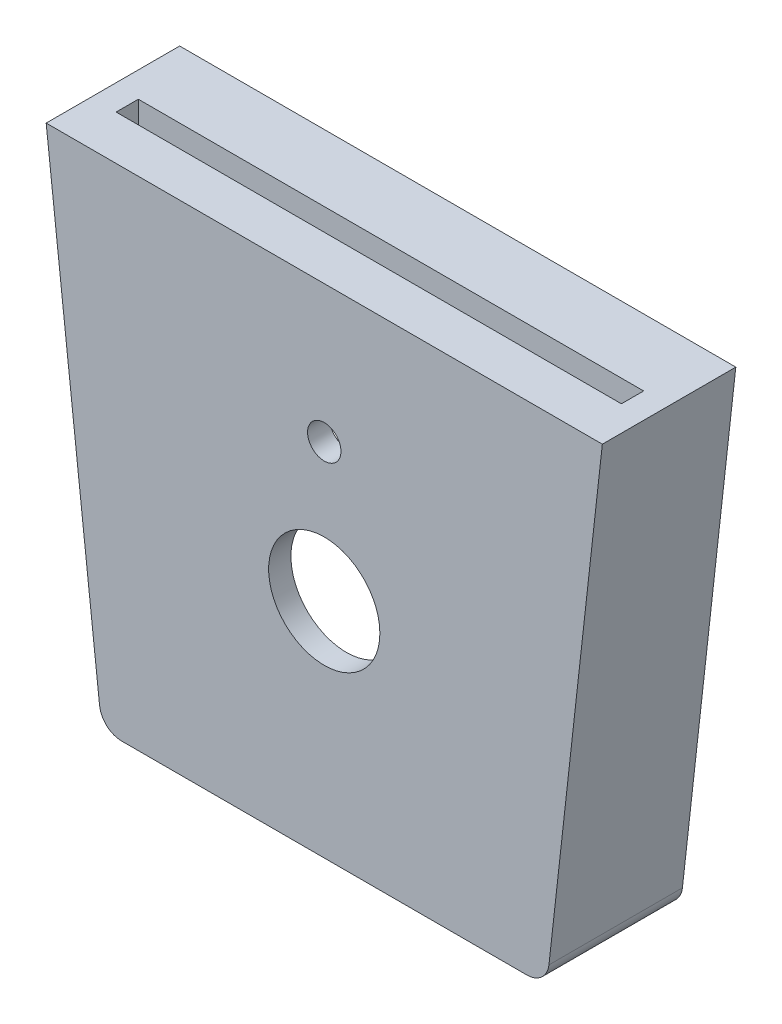
SolidWorks part; units mm, degrees
ref_plane "Front Plane" through (0, 0, 0) normal (0, 0, 1) x (1, 0, 0)
ref_plane "Top Plane" through (0, 0, 0) normal (0, 1, 0) x (1, 0, 0)
ref_plane "Right Plane" through (0, 0, 0) normal (1, 0, 0) x (0, 0, -1)
sketch "Sketch1" plane through (0, 0, 0) normal (0, 0, 1) x (1, 0, 0)
  line L0 (0, 56.7961) -> (0, -56.7961) construction
  line L1 (63.5, 56.7961) -> (-63.5, 56.7961)
  line L2 (-63.5, 56.7961) -> (-51.3049, -52.2806)
  line L3 (-46.2563, -56.7961) -> (46.2563, -56.7961)
  line L4 (63.5, 56.7961) -> (51.3049, -52.2806)
  arc A0 (-51.3049, -52.2806) -> (-46.2563, -56.7961) centre (-46.2563, -51.7161) ccw
  arc A1 (51.3049, -52.2806) -> (46.2563, -56.7961) centre (46.2563, -51.7161) cw
  circle A2 centre (0, 25.5165) radius 3.81
  circle A3 centre (0, -5.9961) radius 12.7
  point P10 (-50.8, -56.7961)
  dimension "D4" = 5.08
  dimension "D6" = 7.62
  dimension "D7" = 25.4
  dimension "D8" = 31.2797
  dimension "D9" = 50.8
  dimension "D1" = 50.8
  dimension "D2" = 63.5
  dimension "D3" = 56.7961
  dimension "D5" = 109.0767
extrude "Boss-Extrude1" add sketch "Sketch1" against normal blind 5.08
sketch "Sketch2" plane through (0, 0, -5.08) normal (0, 0, 1) x (1, 0, 0)
  line L0 (0, 56.7961) -> (0, -56.7961) construction
  line L1 (63.5, 56.7961) -> (-63.5, 56.7961)
  line L2 (-63.5, 56.7961) -> (-51.3049, -52.2806)
  line L3 (-46.2563, -56.7961) -> (46.2563, -56.7961)
  line L4 (63.5, 56.7961) -> (51.3049, -52.2806)
  line L5 (-46.2563, -56.7961) -> (46.2563, -56.7961) construction
  line L6 (-57.8204, 51.7161) -> (57.8204, 51.7161)
  line L7 (57.8204, 51.7161) -> (46.7612, -47.2006)
  line L8 (41.7126, -51.7161) -> (-41.7126, -51.7161)
  line L9 (-57.8204, 51.7161) -> (-46.7612, -47.2006)
  arc A0 (-51.3049, -52.2806) -> (-46.2563, -56.7961) centre (-46.2563, -51.7161) ccw
  arc A1 (51.3049, -52.2806) -> (46.2563, -56.7961) centre (46.2563, -51.7161) cw
  circle A2 centre (0, 26.1693) radius 3.81
  circle A3 centre (0, -32.9791) radius 12.7
  arc A4 (46.7612, -47.2006) -> (41.7126, -51.7161) centre (41.7126, -46.6361) cw
  arc A5 (-46.7612, -47.2006) -> (-41.7126, -51.7161) centre (-41.7126, -46.6361) ccw
  point P10 (-50.8, -56.7961)
  point P27 (0, -51.7161)
  point P28 (0, 51.7161)
  arc M12 (51.3049, -52.2806) -> (46.2563, -56.7961) centre (46.2563, -51.7161) cw
  line M13 (46.2563, -56.7961) -> (-46.2563, -56.7961)
  arc M14 (-46.2563, -56.7961) -> (-51.3049, -52.2806) centre (-46.2563, -51.7161) cw
  line M15 (-51.3049, -52.2806) -> (-63.5, 56.7961)
  line M16 (-63.5, 56.7961) -> (63.5, 56.7961)
  line M17 (63.5, 56.7961) -> (51.3049, -52.2806)
  dimension "D4" = 5.08
  dimension "D6" = 7.62
  dimension "D7" = 25.4
  dimension "D8" = 30.6268
  dimension "D9" = 23.8171
  dimension "D11" = 5.08
  dimension "D1" = 50.8
  dimension "D2" = 63.5
  dimension "D3" = 5.08
  dimension "D5" = 109.0767
  dimension "D10" = 0
extrude "Boss-Extrude2" add sketch "Sketch2" against normal blind 25.4 contours L0 L1 L8 A4 L7 L6 M17 M12 M13 | L0 L6 L9 A5 L8 L3 M16 M14 M15 region at (31.75, 55.4948, -5.08) region at (-1.3014, 54.2561, -5.08)
sketch "Sketch3" plane through (0, 56.7961, 0) normal (0, 1, 0) x (1, 0, 0)
  line L0 (57.6928, 10.16) -> (57.6928, 15.24)
  line L1 (57.6928, 10.16) -> (-57.6928, 10.16)
  line L2 (57.6928, 15.24) -> (-57.6928, 15.24)
  line L3 (-57.6928, 10.16) -> (-57.6928, 15.24)
  line L6 (63.5, 0) -> (-63.5, 0) construction
  line L8 (-63.5, 30.48) -> (-63.5, 0) construction
  dimension "D1" = 115.3856
  dimension "D2" = 5.8072
  dimension "D3" = 10.16
  dimension "D4" = 5.08
extrude "Cut-Extrude2" cut sketch "Sketch3" against normal blind 6.35
sketch "Sketch4" plane through (0, 0, -30.48) normal (0, 0, -1) x (-1, 0, 0)
  line L0 (0, 51.7161) -> (0, -51.7161) construction
  line L1 (57.8204, 51.7161) -> (-57.8204, 51.7161) construction
  line L2 (-41.7126, -51.7161) -> (41.7126, -51.7161) construction
  line L3 (-52.9958, 8.564) -> (-33.9458, 8.564)
  line L4 (-57.8204, 51.7161) -> (-46.7612, -47.2006) construction
  line L5 (-33.9458, 8.564) -> (-33.9458, -4.136)
  line L6 (-33.9458, -4.136) -> (-51.5759, -4.136)
  line L7 (-57.8204, 51.7161) -> (-46.7612, -47.2006) construction
  line L8 (33.9458, -4.136) -> (51.5759, -4.136)
  line L9 (33.9458, 8.564) -> (33.9458, -4.136)
  line L10 (52.9958, 8.564) -> (33.9458, 8.564)
  line L11 (-51.5759, -4.136) -> (-52.9958, 8.564)
  line L12 (52.9958, 8.564) -> (51.5759, -4.136)
  dimension "D1" = 19.05
  dimension "D2" = 12.7
  dimension "D3" = 33.9458
extrude "Boss-Extrude3" add sketch "Sketch4" against normal blind 2.54
sketch "Sketch5" plane through (0, 0, -30.48) normal (0, 0, -1) x (-1, 0, 0)
  line L0 (-43.4708, 8.564) -> (-42.7609, -4.136) construction
  line L1 (-33.9458, 8.564) -> (-52.9958, 8.564) construction
  line L2 (-51.5759, -4.136) -> (-33.9458, -4.136) construction
  line L3 (0, 51.7161) -> (0, -51.7161) construction
  line L4 (57.8204, 51.7161) -> (-57.8204, 51.7161) construction
  line L5 (-41.7126, -51.7161) -> (41.7126, -51.7161) construction
  circle A0 centre (-43.1159, 2.214) radius 1.905
  circle A1 centre (43.1159, 2.214) radius 1.905
  dimension "D1" = 3.81
extrude "Cut-Extrude3" cut sketch "Sketch5" against normal blind 2.54
